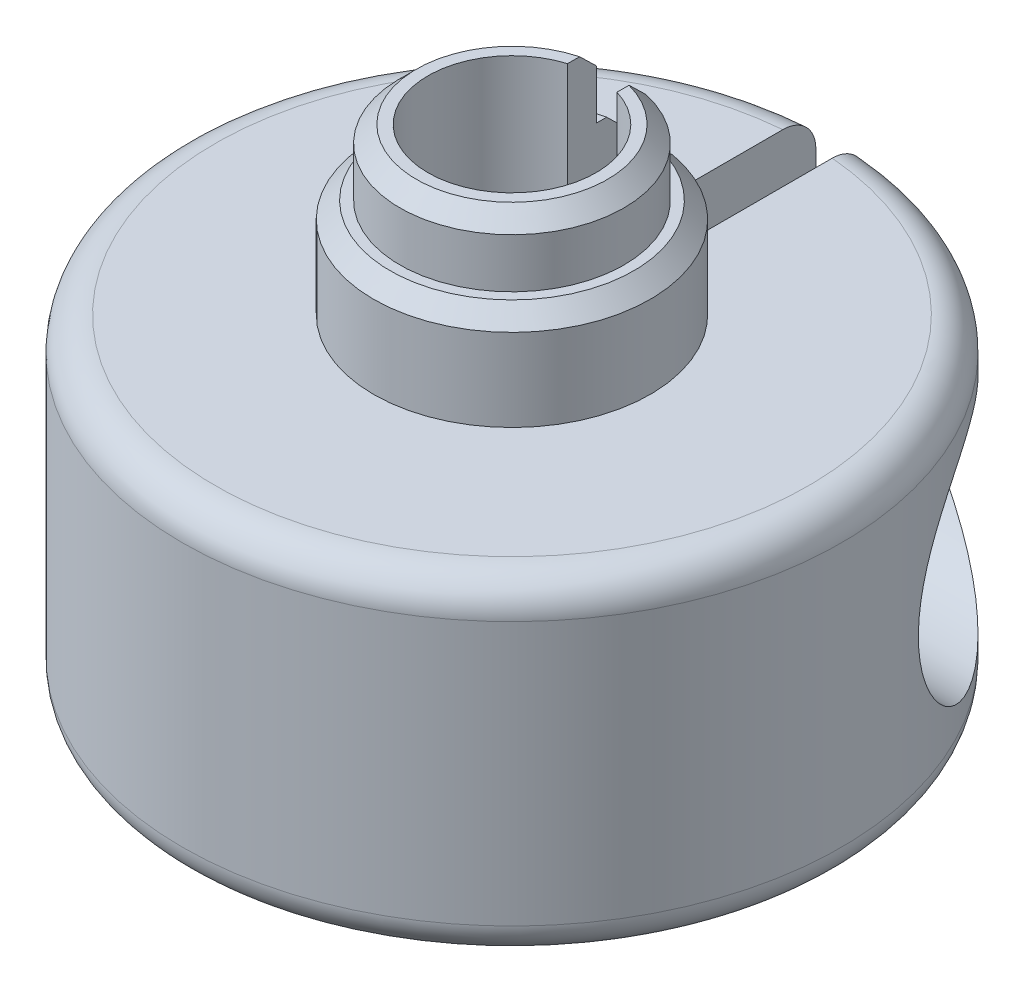
SolidWorks part; units mm, degrees
ref_plane "Front Plane" through (0, 0, 0) normal (0, 0, 1) x (1, 0, 0)
ref_plane "Top Plane" through (0, 0, 0) normal (0, 1, 0) x (1, 0, 0)
ref_plane "Right Plane" through (0, 0, 0) normal (1, 0, 0) x (0, 0, -1)
sketch "Sketch1" plane through (0, 0, 0) normal (0, 1, 0) x (1, 0, 0)
  circle A0 centre (0, 0) radius 4.05
  dimension "D1" = 8.1
extrude "Boss-Extrude1" add sketch "Sketch1" along normal blind 8
sketch "Sketch2" plane through (0, 8, 0) normal (0, 1, 0) x (1, 0, 0)
  circle A0 centre (0, 0) radius 10
  dimension "D1" = 20
extrude "Boss-Extrude2" add sketch "Sketch2" along normal blind 10
fillet "Fillet1" radius 1 3 edges at (0, 0, 4.05) (0, 8, 10) (0, 18, 10)
sketch "Sketch3" plane through (0, 18, 0) normal (0, 1, 0) x (1, 0, 0)
  circle A0 centre (0, 0) radius 2.55
  dimension "D1" = 5.1
extrude "Cut-Extrude1" cut sketch "Sketch3" against normal blind 10 contours A0
sketch "Sketch20" plane through (0, 18, 0) normal (0, 1, 0) x (1, 0, 0)
  line L1 (-0.75, 2.4372) -> (0.75, 2.4372)
  line L2 (-0.75, 2.4372) -> (-0.75, 9.9718)
  line L4 (0.75, 2.4372) -> (0.75, 9.9718)
  circle A0 centre (0, 0) radius 2.55 construction
  circle A1 centre (0, 0) radius 2.55 construction
  circle A2 centre (0, 0) radius 10 construction
  arc A3 (0.75, 9.9718) -> (-0.75, 9.9718) centre (0, 0) ccw
  dimension "D1" = 1.5
extrude "Cut-Extrude2" cut sketch "Sketch20" against normal up to surface (10 mm away) up to face at (0, 8, 9)
ref_plane "Plane2" through (10, 0, 0) normal (1, 0, 0) x (0, 0, -1)
sketch "Sketch32" plane through (10, 0, 0) normal (1, 0, 0) x (0, 0, -1)
  line L0 (9.9718, 9) -> (9.9718, 17) construction
  line L1 (9.9718, 9) -> (9.9718, 17) construction
  line L2 (2.4372, 8) -> (2.4372, 18) construction
  line L3 (2.4372, 8) -> (2.4372, 18) construction
  line L4 (2.4372, 13) -> (9.9718, 13) construction
  point P0 (6.2045, 13)
  point P5 (9.9718, 13)
  point P17 (6.2045, 13)
hole_wizard "M2.5 Clearance Hole1" positions "Sketch32" profile "Sketch26" hole size "M2.5" standard "ANSI Metric" end condition through all
sketch "Sketch26" plane through (10, 13, -6.2045) normal (0, 1, 0) x (0, 0, -1)
  line L0 (0, 0) -> (0, 20)
  line L1 (0, 20) -> (1.45, 20)
  line L2 (1.45, 20) -> (1.45, 0)
  line L5 (1.45, 0) -> (0, 0)
  line L11 (0, -6.35) -> (0, 107.95) construction
  dimension "Thru Hole Dia." = 2.9
  dimension "Thru Hole Depth" = 20
sketch "Sketch28" plane through (10, 0, 0) normal (1, 0, 0) x (0, 0, -1)
  circle A0 centre (6.2045, 13) radius 1.45 construction
  circle A1 centre (6.2045, 13) radius 1.45 construction
  circle A2 centre (6.2045, 13) radius 3.5
  dimension "D1" = 7
extrude "Cut-Extrude3" cut sketch "Sketch28" against normal blind 6.5
sketch "Sketch29" plane through (0, 0, 0) normal (0, 0, 1) x (1, 0, 0)
  line L0 (-4.05, 8) -> (-4.05, 1) construction
  line L1 (4.05, 8) -> (-4.05, 8)
  line L2 (4.05, 8) -> (4.05, 7.5)
  line L3 (4.05, 7.5) -> (-4.05, 7.5)
  line L4 (-4.05, 8) -> (-4.05, 7.5)
  dimension "D1" = 0.5
extrude "Cut-Extrude7" cut sketch "Sketch29" against normal through all
fillet "Fillet2" radius 0.25 3 edges at (3.3, 8, 0) (-3.3, 8, 0) (0, 7.5, 0)
sketch "Sketch30" plane through (0, 18, 0) normal (0, 1, 0) x (1, 0, 0)
  line L0 (-0.75, 8.9687) -> (-0.75, 2.4372) construction
  line L1 (0.75, 2.4372) -> (0.75, 8.9687) construction
  line L2 (-0.75, 3.3162) -> (-0.75, 2.4372)
  line L3 (0.75, 2.4372) -> (0.75, 3.3162)
  arc A0 (-0.75, 2.4372) -> (0.75, 2.4372) centre (0, 0) ccw
  arc A1 (-0.75, 3.3162) -> (0.75, 3.3162) centre (0, 0) ccw
  dimension "D1" = 3.4
extrude "Boss-Extrude3" add sketch "Sketch30" along normal blind 5
chamfer "Chamfer1" distance 0.5 angle 45 1 edges at (0, 23, 3.4)
ref_plane "Plane3" through (-10, 0, 0) normal (-1, 0, 0) x (0, 0, 1)
sketch "Sketch33" plane through (-10, 0, 0) normal (-1, 0, 0) x (0, 0, 1)
  line L0 (-3.3162, 18) -> (-8.9687, 18) construction
  line L1 (-3.1446, 13) -> (-4.6745, 15.65)
  line L2 (-4.6745, 15.65) -> (-7.7345, 15.65)
  line L3 (-7.7345, 15.65) -> (-9.2645, 13)
  line L4 (-9.2645, 13) -> (-7.7345, 10.35)
  line L5 (-7.7345, 10.35) -> (-4.6745, 10.35)
  line L6 (-4.6745, 10.35) -> (-3.1446, 13)
  circle A0 centre (-6.2045, 13) radius 2.65 construction
  dimension "D1" = 5.3
extrude "Cut-Extrude8" cut sketch "Sketch33" against normal blind 7
sketch "Sketch34" plane through (0, 23, 0) normal (0, 1, 0) x (1, 0, 0)
  line L0 (-0.75, 3.3162) -> (-0.75, 4.1325)
  line L1 (0.75, 3.3162) -> (0.75, 4.1325)
  line L2 (0.75, 3.3162) -> (0.75, 8.9687) construction
  arc A0 (-0.75, 4.1325) -> (0.75, 4.1325) centre (0, 0) ccw
  arc A1 (-0.75, 3.3162) -> (0.75, 3.3162) centre (0, 0) ccw
  dimension "D1" = 4.2
extrude "Boss-Extrude4" add sketch "Sketch34" along normal blind 3 from surface starting at face at (0, 18, 0.0288)
chamfer "Chamfer2" distance 0.5 angle 45 1 edges at (0, 21, 4.2)
sketch "Sketch35" plane through (0, 0, 0) normal (0, -1, 0) x (1, 0, 0)
  circle A0 centre (0, 0) radius 4.05
extrude "Cut-Extrude9" cut sketch "Sketch35" against normal up to surface (8 mm away) up to face at (0, 8, -0.2604)
equation "\"1.5.00mm\"=6"
